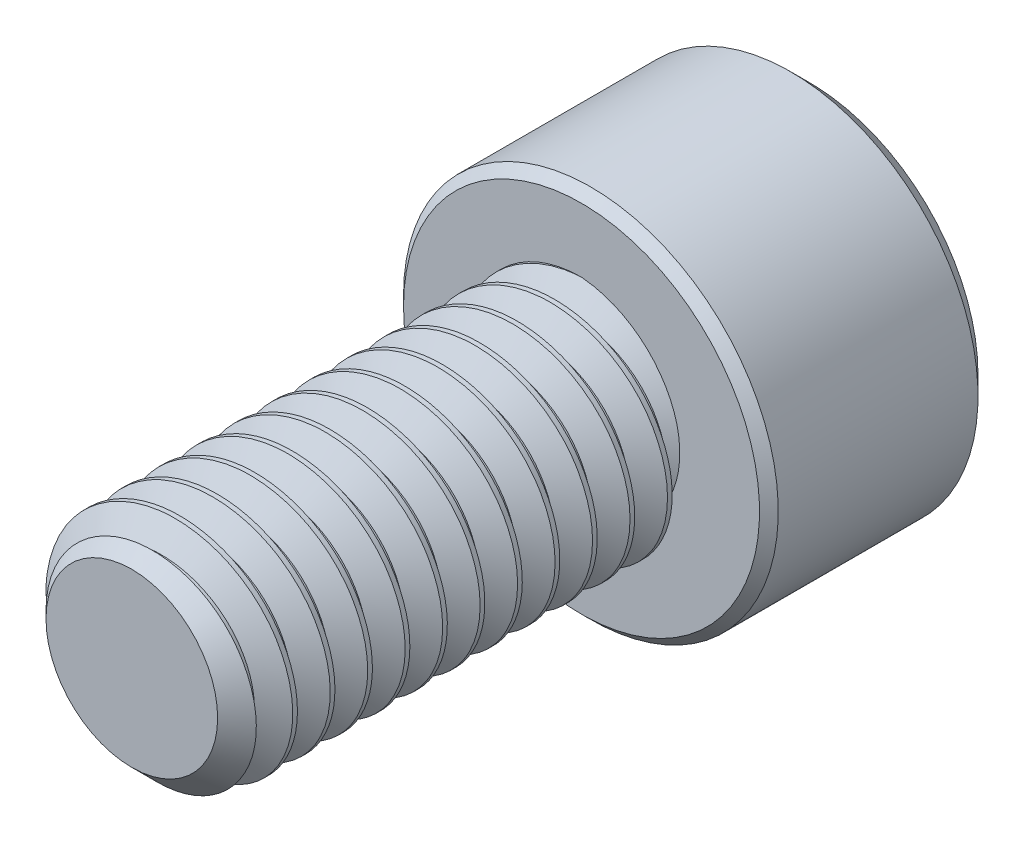
SolidWorks part; units mm, degrees
ref_plane "Front Plane" through (0, 0, 0) normal (0, 0, 1) x (1, 0, 0)
ref_plane "Top Plane" through (0, 0, 0) normal (0, 1, 0) x (1, 0, 0)
ref_plane "Right Plane" through (0, 0, 0) normal (1, 0, 0) x (0, 0, -1)
sketch "Sketch0" plane through (0, 0, 0) normal (1, 0, 0) x (0, 0, -1)
  line L0 (0, 0) -> (9.525, 0) construction
  point P2 (14.351, 0)
  point P4 (0, 0)
  dimension "D1" = 9.525
  dimension "D2" = 4.826
  dimension "Min Thread" = 0
sketch "Sketch1" plane through (0, 0, 0) normal (0, 0, 1) x (1, 0, 0)
  circle A0 centre (0, 0) radius 2.413
  dimension "OD" = 4.826
extrude "Extrude1" add sketch "Sketch1" against normal blind 9.525
sketch "Sketch2" plane through (0, 0, 0) normal (0, 0, 1) x (1, 0, 0)
  circle A0 centre (0, 0) radius 2.413 construction
  circle A1 centre (0, 0) radius 2.413
curve "Helix/Spiral1" pitch 0.7937 height 10.3188 turns 13 parameters "pitch"=0.7937
chamfer "Chamfer3" distance 0.5953 angle 45 1 edges at (2.413, 0, 0)
sketch "Sketch3" plane through (0, 0, 0) normal (1, 0, 0) x (0, 0, -1)
  line L0 (-0.6945, 2.413) -> (-0.3969, 1.8974)
  line L1 (-0.3969, 1.8974) -> (-0.2977, 1.8974)
  line L2 (-0.2977, 1.8974) -> (0, 2.413)
  line L3 (-0.6945, 2.413) -> (0, 2.413)
  line L4 (-0.3473, 2.413) -> (-0.3473, 1.8974) construction
  line L5 (-0.5457, 2.1552) -> (-0.1488, 2.1552) construction
  line L6 (0, 2.413) -> (0, -2.413) construction
  dimension "D1" = 0.0992
  dimension "D2" = 0.3969
  dimension "D3" = 60
sweep "Cut-Sweep1" cut profiles "Sketch3" path "Helix/Spiral1"
sketch "Sketch5" plane through (0, 0, 0) normal (1, 0, 0) x (0, 0, -1)
  line L0 (9.525, -1.9083) -> (9.525, 1.7217) construction
  line L1 (9.525, 2.413) -> (0, 2.413)
  line L2 (9.525, 2.413) -> (9.525, 0)
  line L3 (9.525, 0) -> (-0.8783, 0)
  line L4 (0, 0) -> (9.525, 0) construction
  line L5 (0, 2.413) -> (-0.8783, 0)
  line L6 (0, 0) -> (12.065, 0) construction
  dimension "D1" = 70
  dimension "D3" = 2.54
revolve "partially thread" [suppressed] add sketch "Sketch5" angle 360 about L6
sketch "Sketch6" plane through (0, 0, -9.525) normal (0, 0, -1) x (-1, 0, 0)
  circle A0 centre (0, 0) radius 3.9688
  dimension "head dia" = 7.9375
extrude "Extrude2" add sketch "Sketch6" along normal blind 4.826
sketch "Sketch7" plane through (0, 0, -14.351) normal (0, 0, -1) x (-1, 0, 0)
  line L1 (0, 2.2914) -> (-1.9844, 1.1457)
  line L2 (-1.9844, 1.1457) -> (-1.9844, -1.1457)
  line L3 (-1.9844, -1.1457) -> (0, -2.2914)
  line L4 (0, -2.2914) -> (1.9844, -1.1457)
  line L5 (1.9844, -1.1457) -> (1.9844, 1.1457)
  line L6 (1.9844, 1.1457) -> (0, 2.2914)
  circle A0 centre (0, 0) radius 1.9844 construction
  dimension "hex dia" = 3.9688
extrude "Cut-Extrude1" cut sketch "Sketch7" against normal blind 2.9766
sketch "Sketch8" plane through (0, 0, -14.351) normal (0, 0, -1) x (-1, 0, 0)
  circle A0 centre (0, 0) radius 2.2914
extrude "Cut-Extrude2" cut sketch "Sketch8" against normal through all draft 45
chamfer "Chamfer1" distance 0.3969 angle 45 1 edges at (-3.9688, 0, -14.351)
chamfer "Chamfer2" distance 0.1984 angle 45 1 edges at (-3.9688, 0, -9.525)
sketch "Sketch9" plane through (0, 0, 0) normal (1, 0, 0) x (0, 0, -1)
  line L0 (0, 2.413) -> (0, -2.413) construction
  line L1 (1.9844, 2.413) -> (1.9844, -2.413) construction
  line L2 (14.351, 3.9688) -> (14.351, -3.9688) construction
  line L3 (9.525, 3.9688) -> (9.525, -3.9688) construction
  line L4 (9.525, 3.7703) -> (9.525, -3.7703) construction
  line L5 (14.351, -3.5719) -> (14.351, 3.5719) construction
  line L6 (9.525, -3.9688) -> (9.525, 3.9688) construction
  line L7 (0, 1.8177) -> (0, -1.8177) construction
  line L8 (-0.6945, 2.413) -> (0, 2.413) construction
  line L9 (1.9844, 0) -> (0, 0) construction
  dimension "D1" = 1.9844
equation "\"D3@Helix/Spiral1\" = \"screw length@Extrude1\"+\"pitch@Helix/Spiral1\""
equation "\"D1@Sketch3\" = \"pitch@Helix/Spiral1\"*.125"
equation "\"D2@Sketch3\" = \"pitch@Helix/Spiral1\"*.5"
equation "\"D1@Cut-Extrude1\" = \"hex dia@Sketch7\"*.75"
equation "\"D1@Chamfer1\" = \"head dia@Sketch6\"*.05"
equation "\"D1@Sketch9\" = \"pitch@Helix/Spiral1\"*2.50"
equation "\"D1@Chamfer2\" = \"D1@Chamfer1\"/2"
equation "\"D1@Chamfer3\" = \"pitch@Helix/Spiral1\"*.750"
equation "\"D1@Sketch0\" = \"screw length@Extrude1\""
equation "\"D2@Sketch0\" = \"head depth@Extrude2\""
